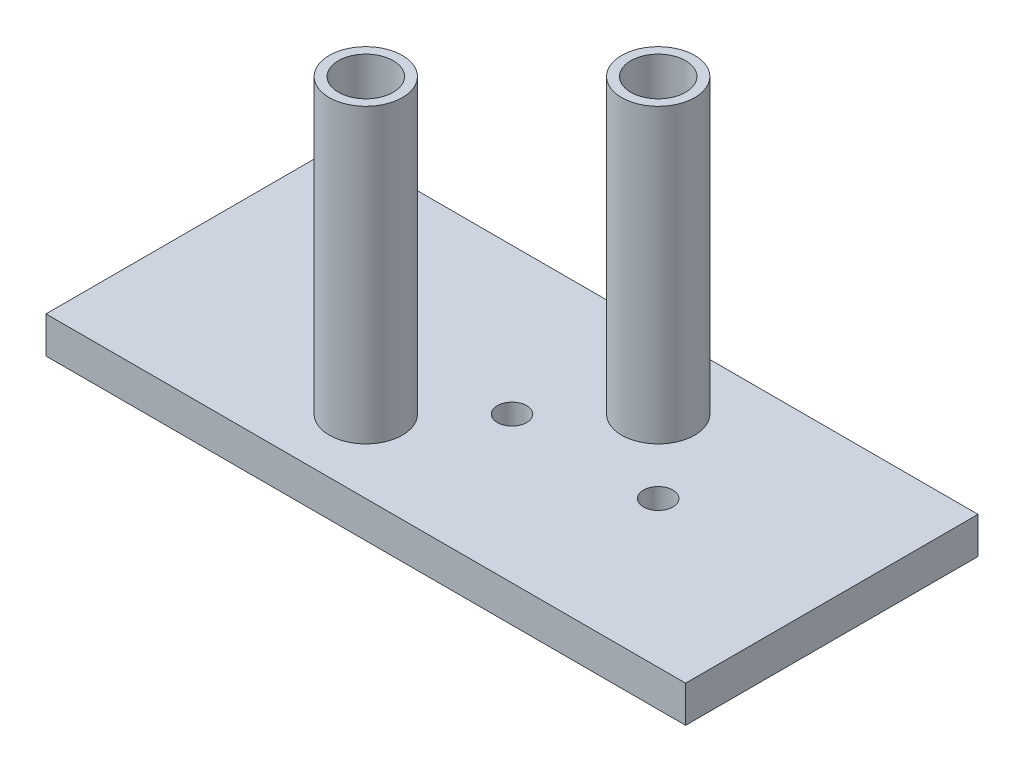
SolidWorks part; units mm, degrees
ref_plane "Front Plane" through (0, 0, 0) normal (0, 0, 1) x (1, 0, 0)
ref_plane "Top Plane" through (0, 0, 0) normal (0, 1, 0) x (1, 0, 0)
ref_plane "Right Plane" through (0, 0, 0) normal (1, 0, 0) x (0, 0, -1)
sketch "Sketch1" plane through (0, 0, 0) normal (0, 1, 0) x (1, 0, 0)
  line L1 (0, 0) -> (-111.125, 0)
  line L2 (0, 0) -> (0, -50.8)
  line L3 (0, -50.8) -> (-111.125, -50.8)
  line L4 (-111.125, 0) -> (-111.125, -50.8)
  dimension "D1" = 111.125
  dimension "D2" = 50.8
extrude "Boss-Extrude1" add sketch "Sketch1" along normal blind 6.35 contours L2 L1 L4 L3
sketch "Sketch2" plane through (0, 6.35, 0) normal (0, 1, 0) x (1, 0, 0)
  line L0 (0, -50.8) -> (-111.125, -50.8) construction
  line L1 (0, 0) -> (0, -50.8) construction
  circle A0 centre (-55.5625, -25.4) radius 2.5527
  circle A1 centre (-30.1625, -25.4) radius 2.5527
  circle A2 centre (-80.9625, -25.4) radius 2.5527
  circle A3 centre (-68.2625, -38.1) radius 9.525 construction
  circle A4 centre (-42.8625, -12.7) radius 9.525 construction
  circle A5 centre (-42.8625, -12.7) radius 6.35
  circle A6 centre (-68.2625, -38.1) radius 6.35
  circle A8 centre (-42.8625, -12.7) radius 4.7625
  circle A9 centre (-68.2625, -38.1) radius 4.7625
  point P10 (-55.5625, -50.8)
  point P23 (0, -25.4)
  dimension "D1" = 25.4
  dimension "D3" = 12.7
  dimension "D2" = 25.4
  dimension "D4" = 12.7
  dimension "D5" = 12.7
  dimension "D6" = 12.7
extrude "Boss-Extrude2" add sketch "Sketch2" along normal blind 50.8 contours A8 | A5 | A9 | A6
extrude "Cut-Extrude1" cut sketch "Sketch2<9>" against normal through all contours A1 | A2 | A0
sketch "Sketch2<9>" plane through (0, 6.35, 0) normal (0, 1, 0) x (1, 0, 0) same geometry as "Sketch2"
